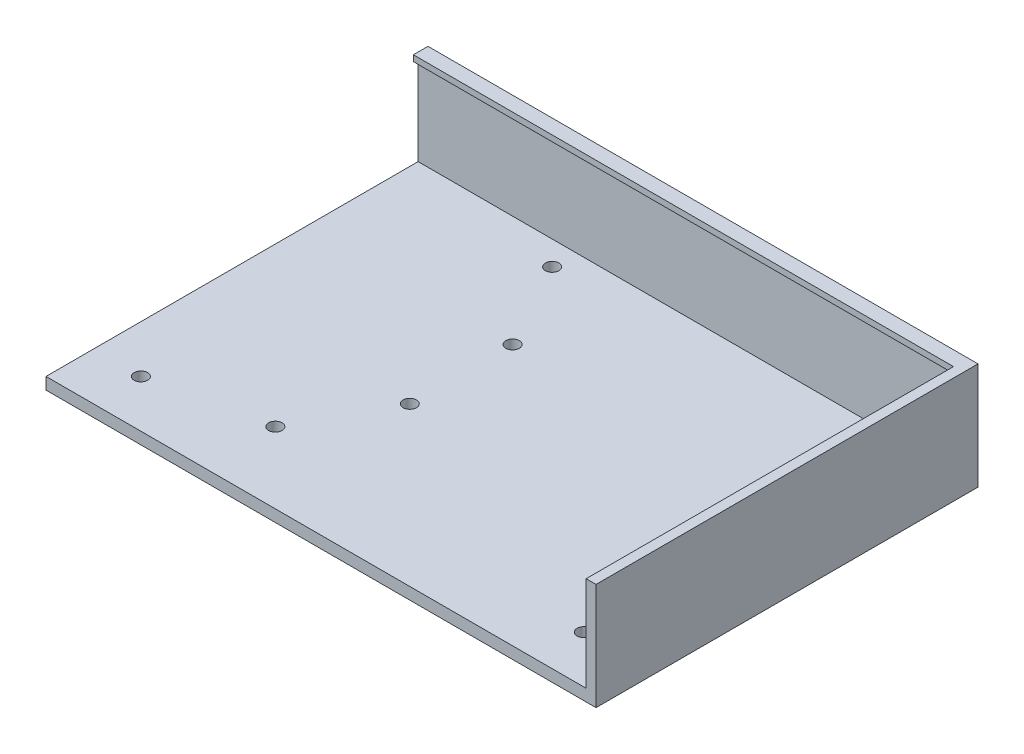
SolidWorks part; units mm, degrees
ref_plane "Front Plane" through (0, 0, 0) normal (0, 0, 1) x (1, 0, 0)
ref_plane "Top Plane" through (0, 0, 0) normal (0, 1, 0) x (1, 0, 0)
ref_plane "Right Plane" through (0, 0, 0) normal (1, 0, 0) x (0, 0, -1)
sketch "Sketch1" plane through (0, 0, 0) normal (0, 1, 0) x (1, 0, 0)
  line L1 (-139.1, -96.6) -> (139.1, -96.6)
  line L2 (-139.1, -96.6) -> (-139.1, 96.6)
  line L3 (-139.1, 96.6) -> (139.1, 96.6)
  line L4 (139.1, -96.6) -> (139.1, 96.6)
  line L5 (-139.1, -96.6) -> (139.1, 96.6) construction
  line L6 (-139.1, 96.6) -> (139.1, -96.6) construction
  point P0 (0, 0)
  dimension "D1" = 278.2
  dimension "D2" = 193.2
extrude "Shell Block" add sketch "Sketch1" along normal blind 27
ref_plane "Shell Front" through (0, 27, 0) normal (0, 1, 0) x (1, 0, 0)
sketch "Sketch2" plane through (0, 27, 0) normal (0, 1, 0) x (1, 0, 0)
  line L1 (-136.6, -92.9) -> (136.6, -92.9)
  line L2 (-136.6, -92.9) -> (-136.6, 92.9)
  line L3 (-136.6, 92.9) -> (136.6, 92.9)
  line L4 (136.6, -92.9) -> (136.6, 92.9)
  line L5 (-136.6, -92.9) -> (136.6, 92.9) construction
  line L6 (-136.6, 92.9) -> (136.6, -92.9) construction
  point P0 (0, 0)
  dimension "D1" = 273.2
  dimension "D2" = 185.8
extrude "Front Opening" cut sketch "Sketch2" against normal blind 1.5
ref_plane "Under Lip" through (0, 25.5, 0) normal (0, 1, 0) x (1, 0, 0)
sketch "Sketch3" plane through (0, 25.5, 0) normal (0, 1, 0) x (1, 0, 0)
  line L1 (-136.6, -94.1) -> (136.6, -94.1)
  line L2 (-136.6, -94.1) -> (-136.6, 94.1)
  line L3 (-136.6, 94.1) -> (136.6, 94.1)
  line L4 (136.6, -94.1) -> (136.6, 94.1)
  line L5 (-136.6, -94.1) -> (136.6, 94.1) construction
  line L6 (-136.6, 94.1) -> (136.6, -94.1) construction
  point P0 (0, 0)
  dimension "D1" = 273.2
  dimension "D2" = 188.2
extrude "Display Pocket" cut sketch "Sketch3" against normal blind 22.5
ref_plane "Back Inner" through (0, 3, 0) normal (0, 1, 0) x (1, 0, 0)
sketch "Sketch4" plane through (0, 3, 0) normal (0, 1, 0) x (1, 0, 0)
  line L1 (-69, 28) -> (-66, 28)
  line L2 (-69, 28) -> (-69, 84)
  line L3 (-69, 84) -> (-66, 84)
  line L4 (-66, 28) -> (-66, 84)
  line L6 (-69, -84) -> (-66, -84)
  line L7 (-69, -84) -> (-69, -28)
  line L8 (-69, -28) -> (-66, -28)
  line L9 (-66, -84) -> (-66, -28)
  line L11 (-77, 28) -> (-74, 28)
  line L12 (-77, 28) -> (-77, 84)
  line L13 (-77, 84) -> (-74, 84)
  line L14 (-74, 28) -> (-74, 84)
  line L16 (-77, -84) -> (-74, -84)
  line L17 (-77, -84) -> (-77, -28)
  line L18 (-77, -28) -> (-74, -28)
  line L19 (-74, -84) -> (-74, -28)
  line L21 (-85, 28) -> (-82, 28)
  line L22 (-85, 28) -> (-85, 84)
  line L23 (-85, 84) -> (-82, 84)
  line L24 (-82, 28) -> (-82, 84)
  line L26 (-85, -84) -> (-82, -84)
  line L27 (-85, -84) -> (-85, -28)
  line L28 (-85, -28) -> (-82, -28)
  line L29 (-82, -84) -> (-82, -28)
  line L31 (-93, 28) -> (-90, 28)
  line L32 (-93, 28) -> (-93, 84)
  line L33 (-93, 84) -> (-90, 84)
  line L34 (-90, 28) -> (-90, 84)
  line L36 (-93, -84) -> (-90, -84)
  line L37 (-93, -84) -> (-93, -28)
  line L38 (-93, -28) -> (-90, -28)
  line L39 (-90, -84) -> (-90, -28)
  line L41 (-101, 28) -> (-98, 28)
  line L42 (-101, 28) -> (-101, 84)
  line L43 (-101, 84) -> (-98, 84)
  line L44 (-98, 28) -> (-98, 84)
  line L46 (-101, -84) -> (-98, -84)
  line L47 (-101, -84) -> (-101, -28)
  line L48 (-101, -28) -> (-98, -28)
  line L49 (-98, -84) -> (-98, -28)
  line L51 (-109, 28) -> (-106, 28)
  line L52 (-109, 28) -> (-109, 84)
  line L53 (-109, 84) -> (-106, 84)
  line L54 (-106, 28) -> (-106, 84)
  line L56 (-109, -84) -> (-106, -84)
  line L57 (-109, -84) -> (-109, -28)
  line L58 (-109, -28) -> (-106, -28)
  line L59 (-106, -84) -> (-106, -28)
  line L61 (-117, 28) -> (-114, 28)
  line L62 (-117, 28) -> (-117, 84)
  line L63 (-117, 84) -> (-114, 84)
  line L64 (-114, 28) -> (-114, 84)
  line L66 (-117, -84) -> (-114, -84)
  line L67 (-117, -84) -> (-117, -28)
  line L68 (-117, -28) -> (-114, -28)
  line L69 (-114, -84) -> (-114, -28)
  line L71 (-125, 28) -> (-122, 28)
  line L72 (-125, 28) -> (-125, 84)
  line L73 (-125, 84) -> (-122, 84)
  line L74 (-122, 28) -> (-122, 84)
  line L76 (-125, -84) -> (-122, -84)
  line L77 (-125, -84) -> (-125, -28)
  line L78 (-125, -28) -> (-122, -28)
  line L79 (-122, -84) -> (-122, -28)
extrude "Vent Slots" cut sketch "Sketch4" against normal blind 4
sketch "Sketch5" plane through (0, 0, 0) normal (1, 0, 0) x (0, 0, -1)
  line L1 (-29, 5) -> (29, 5)
  line L2 (-29, 5) -> (-29, 21)
  line L3 (-29, 21) -> (29, 21)
  line L4 (29, 5) -> (29, 21)
extrude "Cable Exit (-X short side)" cut sketch "Sketch5" against normal blind 140.1
sketch "Sketch6" plane through (0, 3, 0) normal (0, 1, 0) x (1, 0, 0)
  circle A0 centre (-40, 18) radius 1.7
  circle A1 centre (-40, 88) radius 1.7
  circle A2 centre (40, 18) radius 1.7
  circle A3 centre (40, 88) radius 1.7
  circle A4 centre (-52, 40) radius 1.7
  circle A5 centre (-52, 66) radius 1.7
  circle A6 centre (52, 40) radius 1.7
  circle A7 centre (52, 66) radius 1.7
  circle A8 centre (-12, -82) radius 1.7
  circle A9 centre (12, -82) radius 1.7
  circle A10 centre (124, -12) radius 1.7
  circle A11 centre (124, 12) radius 1.7
  circle A12 centre (-12, -12) radius 1.7
  circle A13 centre (-12, 12) radius 1.7
  circle A14 centre (12, -12) radius 1.7
  circle A15 centre (12, 12) radius 1.7
  circle A16 centre (-110, 12) radius 1.7
  circle A17 centre (-110, -12) radius 1.7
  circle A18 centre (-86, 12) radius 1.7
  circle A19 centre (-86, -12) radius 1.7
extrude "Bolt Holes" cut sketch "Sketch6" against normal blind 4
sketch "Sketch7" plane through (0, 0, 0) normal (0, 1, 0) x (1, 0, 0)
  line L1 (-200, -200) -> (0, -200)
  line L2 (-200, -200) -> (-200, 200)
  line L3 (-200, 200) -> (0, 200)
  line L4 (0, -200) -> (0, 200)
extrude "Keep one half (X)" cut sketch "Sketch7" against normal through all and the other way through all
sketch "Sketch8" plane through (0, 0, 0) normal (0, 1, 0) x (1, 0, 0)
  line L1 (-200, 0) -> (200, 0)
  line L2 (-200, 0) -> (-200, -200)
  line L3 (-200, -200) -> (200, -200)
  line L4 (200, 0) -> (200, -200)
extrude "Keep one quarter (Z)" cut sketch "Sketch8" against normal through all and the other way through all
equation "\"DispL\"= 272.0"
equation "\"DispW\"= 187.0"
equation "\"DispT\"= 20.0"
equation "\"Clr\"= 0.6"
equation "\"Wall\"= 2.5"
equation "\"BackT\"= 3.0"
equation "\"CableRoom\"= 4.0"
equation "\"LipW\"= 1.2"
equation "\"LipT\"= 1.5"
equation "\"CableW\"= 58.0"
equation "\"CableH\"= 16.0"
equation "\"BoltD\"= 3.4"
equation "\"ShellL\"= \"DispL\" + 2 * \"Clr\" + 2 * \"Wall\""
equation "\"ShellW\"= \"DispW\" + 2 * \"Clr\" + 2 * \"Wall\""
equation "\"ShellH\"= \"BackT\" + \"DispT\" + \"CableRoom\""
equation "\"D1@Sketch1\" = \"ShellL\""
equation "\"D2@Sketch1\" = \"ShellW\""
equation "\"D1@Shell Block\" = \"ShellH\""
equation "\"D1@Shell Front\" = \"ShellH\""
equation "\"D1@Sketch2\" = \"DispL\" + 2 * \"Clr\""
equation "\"D2@Sketch2\" = \"DispW\" + 2 * \"Clr\" - 2 * \"LipW\""
equation "\"D1@Front Opening\" = \"LipT\""
equation "\"D1@Under Lip\" = \"ShellH\" - \"LipT\""
equation "\"D1@Sketch3\" = \"DispL\" + 2 * \"Clr\""
equation "\"D2@Sketch3\" = \"DispW\" + 2 * \"Clr\""
equation "\"D1@Display Pocket\" = \"ShellH\" - \"LipT\" - \"BackT\""
equation "\"D1@Back Inner\" = \"BackT\""
